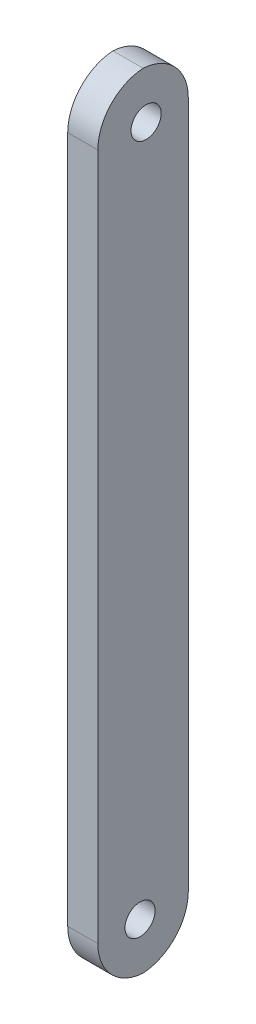
SolidWorks part; units mm, degrees
ref_plane "Plan de face" through (0, 0, 0) normal (0, 0, 1) x (1, 0, 0)
ref_plane "Plan de dessus" through (0, 0, 0) normal (0, 1, 0) x (1, 0, 0)
ref_plane "Plan de droite" through (0, 0, 0) normal (1, 0, 0) x (0, 0, -1)
sketch "Esquisse1" plane through (0, 0, 0) normal (0, 0, 1) x (1, 0, 0)
  line L1 (0, 0) -> (5, 0)
  line L2 (0, 0) -> (0, 130)
  line L3 (0, 130) -> (5, 130)
  line L4 (5, 0) -> (5, 130)
  dimension "D1" = 130
  dimension "D2" = 5
extrude "Boss.-Extru.1" add sketch "Esquisse1" along normal blind 15
fillet "Congé1" radius 8 4 edges at (2.5, 0, 15) (2.5, 0, 0) (2.5, 130, 0) (2.5, 130, 15)
sketch "Esquisse2" plane through (5, 0, 0) normal (1, 0, 0) x (0, 0, -1)
  circle A0 centre (-7, 122) radius 2.5
  circle A1 centre (-8, 8) radius 2.5
extrude "Enlèv. mat.-Extru.1" cut sketch "Esquisse2" against normal blind 15
